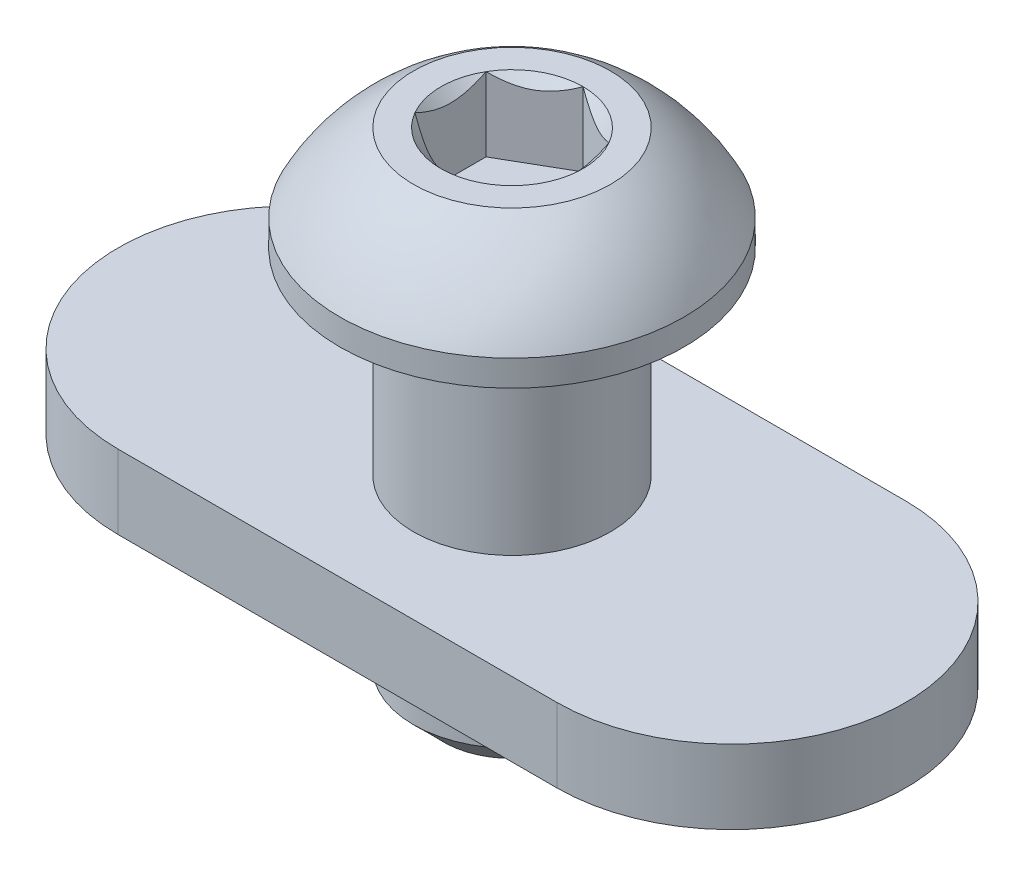
SolidWorks part; units mm, degrees
ref_plane "Front Plane" through (0, 0, 0) normal (0, 0, 1) x (1, 0, 0)
ref_plane "Top Plane" through (0, 0, 0) normal (0, 1, 0) x (1, 0, 0)
ref_plane "Right Plane" through (0, 0, 0) normal (1, 0, 0) x (0, 0, -1)
sketch "Sketch1" plane through (0, 0, 0) normal (0, 1, 0) x (1, 0, 0)
  circle A0 centre (0, 0) radius 3.175
  point P3 (-3.175, 0)
  point P4 (3.175, 0)
  dimension "D1" = 6.35
extrude "Boss-Extrude1" add sketch "Sketch1" against normal blind 12.7
sketch "Sketch2" plane through (0, -12.7, 0) normal (0, -1, 0) x (1, 0, 0)
  circle A1 centre (0, 0) radius 3.175
  circle A2 centre (0, 0) radius 3.175
  point P0 (0, -3.175)
  dimension "D1" = 0
curve "Helix/Spiral1" [suppressed] pitch 1.27 height 13.97 turns 11
sketch "Sketch3" plane through (0, 0, 0) normal (1, 0, 0) x (0, 0, -1)
  line L0 (3.3125, -12.6206) -> (2.2126, -13.2556) construction
  line L1 (2.2126, -13.2556) -> (3.3125, -13.8906) construction
  line L2 (3.3125, -13.8906) -> (3.3125, -12.6206) construction
  line L3 (2.3501, -13.1762) -> (2.3501, -13.335) construction
  line L4 (3.175, -12.7) -> (3.175, -13.8112) construction
  line L5 (2.2126, -13.2556) -> (2.3501, -13.2556) construction
  line L6 (3.175, -13.2556) -> (3.3125, -13.2556) construction
  line L8 (2.2126, -13.2556) -> (-3.175, -13.2556) construction
  line L9 (2.3501, -13.1762) -> (3.2437, -12.6603)
  line L10 (2.3501, -13.1762) -> (2.3501, -13.335)
  line L11 (2.3501, -13.335) -> (3.2437, -13.8509)
  line L12 (3.2437, -13.8509) -> (3.2437, -12.6603)
  line L14 (-3.175, -13.2556) -> (-3.175, -11.9856) construction
  line L15 (-3.175, -11.9856) -> (-3.175, -10.7156) construction
  line L16 (-3.175, -10.7156) -> (-3.175, -9.4456) construction
  line L17 (-3.175, -9.4456) -> (-3.175, -8.1756) construction
  line L18 (-3.175, 0) -> (-3.175, -12.7) construction
  point P15 (3.2437, -13.2556)
  dimension "D1" = 1.27
  dimension "D2" = 0.1588
sweep "Cut-Sweep1" [suppressed] cut profiles "Sketch3" path "Helix/Spiral1"
sketch "Sketch4" plane through (0, -12.7, 0) normal (0, -1, 0) x (1, 0, 0)
  circle A0 centre (0, 0) radius 2.2126
extrude "Cut-Extrude1" cut sketch "Sketch4" against normal blind 1.27 draft 45 flip side to cut
sketch "Sketch5" plane through (0, 0, 0) normal (0, 0, 1) x (1, 0, 0)
  line L0 (0, 0) -> (0, 3.3528)
  line L1 (-5.5499, 0) -> (0, 0)
  line L2 (0, 3.3528) -> (-3.175, 3.3528)
  line L4 (-5.5499, 0.8382) -> (-5.5499, 0)
  line L5 (0, 0) -> (0, -12.7) construction
  arc A0 (-3.175, 3.3528) -> (-5.5499, 0.8382) centre (0, -2.0246) ccw
  dimension "D1" = 3.3528
  dimension "D2" = 0.8382
  dimension "D4" = 11.0998
revolve "Revolve1" add sketch "Sketch5" angle 360 mid plane about L0
sketch "Sketch6" plane through (0, 3.3528, 0) normal (0, 1, 0) x (1, 0, 0)
  line L1 (0, 2.2914) -> (-1.9844, 1.1457)
  line L2 (-1.9844, 1.1457) -> (-1.9844, -1.1457)
  line L3 (-1.9844, -1.1457) -> (0, -2.2914)
  line L4 (0, -2.2914) -> (1.9844, -1.1457)
  line L5 (1.9844, -1.1457) -> (1.9844, 1.1457)
  line L6 (1.9844, 1.1457) -> (0, 2.2914)
  circle A0 centre (0, 0) radius 1.9844 construction
  dimension "D1" = 3.9688
extrude "Cut-Extrude2" cut sketch "Sketch6" against normal blind 2.3813
sketch "Sketch7" plane through (0, 3.3528, 0) normal (0, 1, 0) x (1, 0, 0)
  circle A0 centre (0, 0) radius 2.2914
extrude "Cut-Extrude3" cut sketch "Sketch7" against normal blind 2.3813 draft 45
sketch "Sketch8" plane through (0, 0, 0) normal (0, 1, 0) x (1, 0, 0)
  line L0 (-7.0739, 0) -> (7.0739, 0) construction
  line L1 (-7.0739, 5.6261) -> (7.0739, 5.6261)
  line L2 (-7.0739, -5.6261) -> (7.0739, -5.6261)
  line L4 (-12.7, 5.6261) -> (12.7, 5.6261) construction
  line L5 (-12.7, 5.6261) -> (-12.7, -5.6261) construction
  line L6 (-12.7, -5.6261) -> (12.7, -5.6261) construction
  line L7 (12.7, 5.6261) -> (12.7, -5.6261) construction
  arc A0 (-7.0739, 5.6261) -> (-7.0739, -5.6261) centre (-7.0739, 0) ccw
  arc A1 (7.0739, -5.6261) -> (7.0739, 5.6261) centre (7.0739, 0) ccw
  circle A3 centre (0, 0) radius 3.175
  circle A4 centre (0, 0) radius 3.175
  point P2 (0, 0)
  dimension "D2" = 25.4
  dimension "D3" = 11.2522
  dimension "D1" = 0
extrude "Boss-Extrude2" add sketch "Sketch8" against normal blind 2.3876 from offset 6.35 separate body offset against normal yes
sketch "Sketch9" plane through (0, -8.7376, 0) normal (0, -1, 0) x (1, 0, 0)
  circle A1 centre (0, 0) radius 3.175 construction
  circle A2 centre (0, 0) radius 3.175
  circle A3 centre (0, 0) radius 3.5687
  dimension "D1" = 7.1374
extrude "Boss-Extrude3" add sketch "Sketch9" along normal blind 0.762
sketch "SketchZ" plane through (0, 0, 0) normal (0, 0, 1) x (1, 0, 0)
  line L0 (3.175, -12.9381) -> (3.175, -11.6681) construction
  line L2 (0, -13.2556) -> (0, -11.9856) construction
  line L4 (3.175, -12.9381) -> (0, -12.9381) construction
  line L5 (0, -9.4456) -> (0, -8.1756) construction
  line L6 (0, -12.6206) -> (0, -13.2556) construction
equation "\"D3@Helix/Spiral1\" = \"D4@Helix/Spiral1\" + \"D1@Boss-Extrude1\""
equation "\"D1@Sketch3\" = \"D4@Helix/Spiral1\""
equation "\"D2@Sketch3\" = \"D1@Sketch3\" / 8"
equation "\"D1@Cut-Extrude1\" = \"D4@Helix/Spiral1\""
equation "\"D1@Cut-Extrude2\" = \"D1@Sketch6\" * 3/5"
equation "\"D1@Cut-Extrude3\" = \"D1@Cut-Extrude2\""
equation "\"D2@Sketch5\" = \"D1@Sketch5\" * 1/4"
